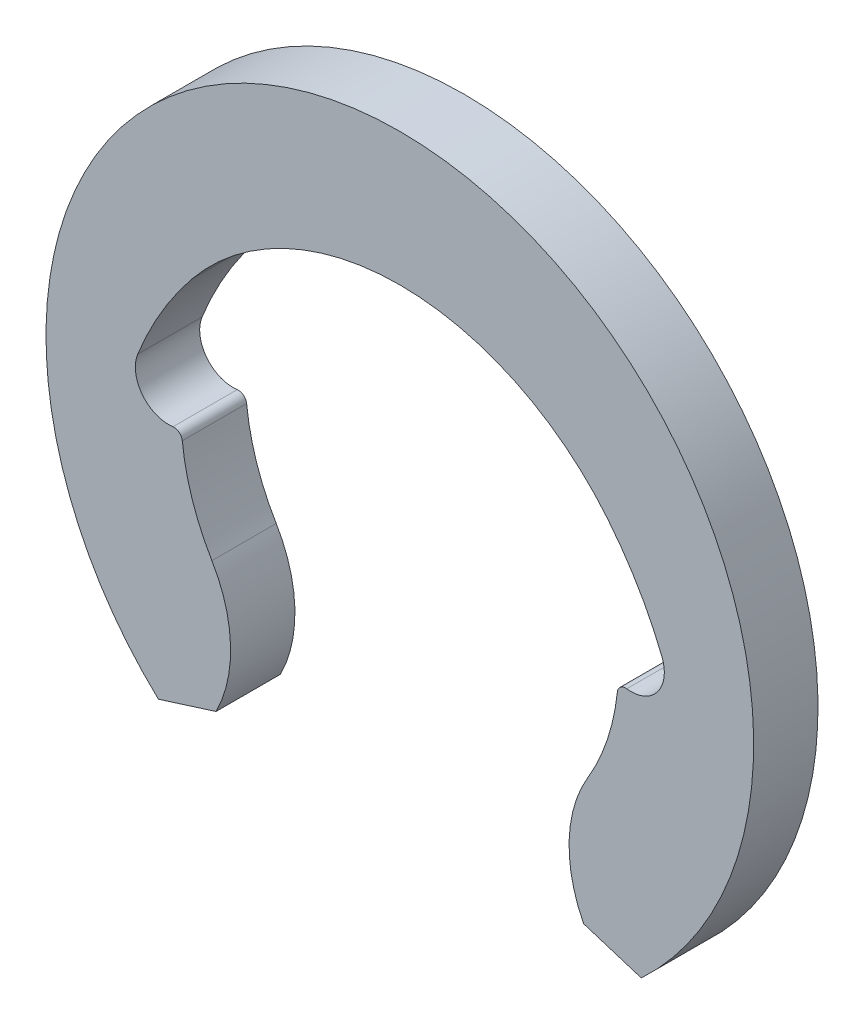
SolidWorks part; units mm, degrees
ref_plane "Front Plane" through (0, 0, 0) normal (0, 0, 1) x (1, 0, 0)
ref_plane "Top Plane" through (0, 0, 0) normal (0, 1, 0) x (1, 0, 0)
ref_plane "Right Plane" through (0, 0, 0) normal (1, 0, 0) x (0, 0, -1)
sketch "Sketch1" plane through (0, 0, 0) normal (0, 0, 1) x (1, 0, 0)
  line L0 (2.4748, 0) -> (-2.7989, 0) construction
  line L1 (0, 2.5848) -> (0, -2.932) construction
  line L2 (0, -0.2095) -> (0, 0.2095) construction
  line L3 (-1.0885, -1.4242) -> (-1.4299, -1.5318)
  line L4 (1.0885, -1.4242) -> (1.4299, -1.5318)
  arc A0 (-1.2883, -0.1352) -> (-1.113, -0.6628) centre (0, 0) ccw
  arc A1 (1.4299, -1.5318) -> (-1.4299, -1.5318) centre (0, 0) ccw
  arc A2 (-1.5524, 0.1766) -> (-1.3437, -0.0916) centre (-1.3696, 0.1036) ccw
  arc A3 (-1.5524, 0.1766) -> (-1.2303, 0.7238) centre (0.3937, -0.6004) cw
  arc A4 (1.5524, 0.1766) -> (1.2303, 0.7238) centre (-0.3937, -0.6004) ccw
  arc A5 (1.113, -0.6628) -> (1.2883, -0.1352) centre (0, 0) ccw
  arc A6 (-1.113, -0.6628) -> (-1.0885, -1.4242) centre (-1.7895, -1.0656) cw
  arc A7 (-1.2883, -0.1352) -> (-1.3437, -0.0916) centre (-1.3373, -0.1404) ccw
  arc A8 (1.113, -0.6628) -> (1.0885, -1.4242) centre (1.7895, -1.0656) ccw
  arc A9 (1.2883, -0.1352) -> (1.3437, -0.0916) centre (1.3373, -0.1404) cw
  arc A10 (1.5524, 0.1766) -> (1.3437, -0.0916) centre (1.3696, 0.1036) cw
  arc A11 (1.2303, 0.7238) -> (-1.2303, 0.7238) centre (0, -0.2794) ccw
  circle A12 centre (0, 0) radius 1.2954 construction
  dimension "D3" = 0.7874
  dimension "D1" = 0.0492
  dimension "D4" = 0.1968
  dimension "D2" = 2.0955
  dimension "D6" = 0.7874
  dimension "D5" = 2.7392
  dimension "D7" = 3.5791
  dimension "D8" = 0.3579
  dimension "D9" = 145
extrude "Extrude1" add sketch "Sketch1" along normal mid plane 0.381
equation "\"D3@Sketch1\" = \"Large_Section@Sketch1\""
equation "\"D6@Sketch1\" = \"Large_Section@Sketch1\""
equation "\"D8@Sketch1\" = \"Large_Section@Sketch1\"/2.2"
equation "\"D7@Sketch1\" = 10*\"D8@Sketch1\""
equation "\"D4@Sketch1\" = \"Large_Section@Sketch1\"/4"
equation "\"D1@Sketch1\" = \"D4@Sketch1\"/4"
equation "\"D5@Sketch1\" = \"Free_Outside_Dia@Sketch1\"/1.53"
equation "\"D2@Sketch1\" = \"Free_Outside_Dia@Sketch1\"/2"
